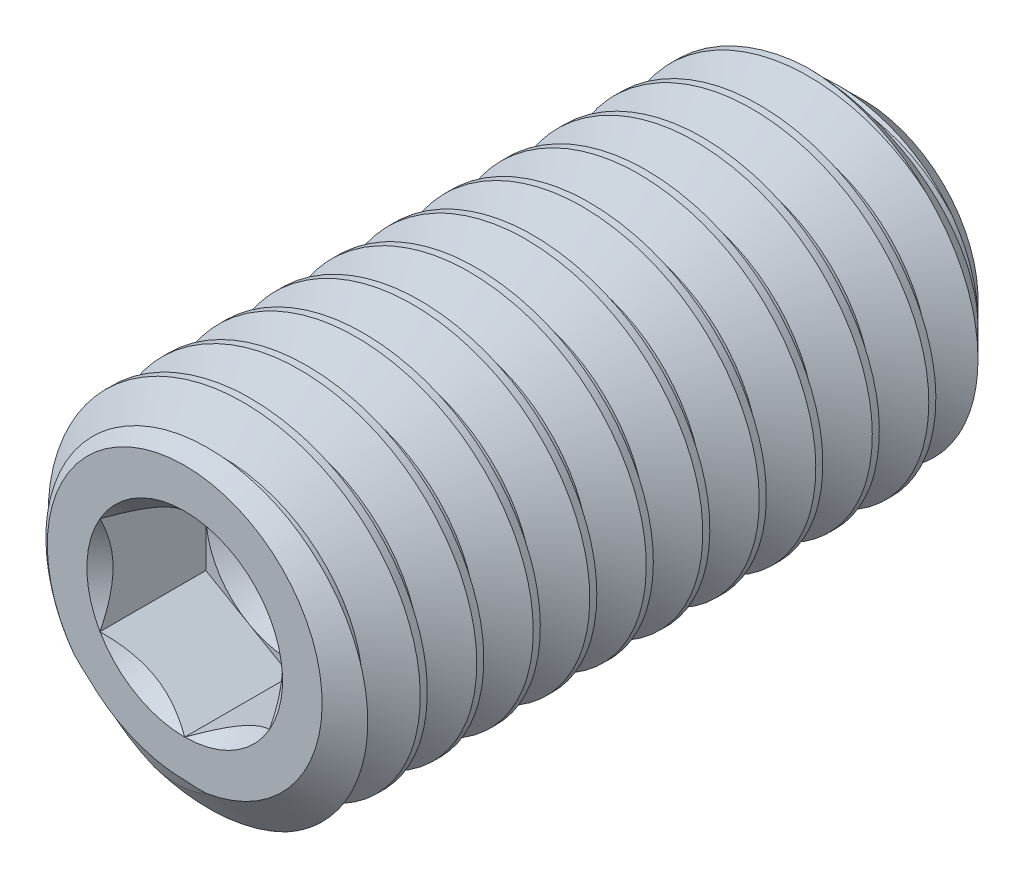
SolidWorks part; units mm, degrees
ref_plane "Front" through (0, 0, 0) normal (0, 0, 1) x (1, 0, 0)
ref_plane "Top" through (0, 0, 0) normal (0, 1, 0) x (1, 0, 0)
ref_plane "Right" through (0, 0, 0) normal (1, 0, 0) x (0, 0, -1)
sketch "Sketch22" plane through (0, 0, 0) normal (1, 0, 0) x (0, 0, -1)
  line L0 (-4.7625, 0) -> (-4.7625, 1.9304)
  line L1 (-4.7625, 1.9304) -> (-4.4246, 2.413)
  line L2 (-4.4246, 2.413) -> (3.9688, 2.413)
  line L3 (3.9688, 2.413) -> (4.7625, 1.6193)
  line L4 (-0.2279, 2.413) -> (-0.2279, -2.413) construction
  line L5 (4.7625, 0) -> (-4.7625, 0)
  line L7 (4.7625, 0) -> (4.7625, 1.6193)
  line L10 (-4.7625, 1.9304) -> (-4.7625, -1.9304) construction
  point P13 (-0.2279, 0)
  dimension "Length" = 9.525
  dimension "D3" = 35
  dimension "D1" = 3.8608
  dimension "Dia" = 4.826
  dimension "D2" = 0.7937
  dimension "D4" = 45
revolve "Revolve1" add sketch "Sketch22" angle 360 about L5
ref_plane "Plane1" through (0, 0, -4.7625) normal (0, 0, 1) x (1, 0, 0)
sketch "Sketch27" plane through (0, 0, -4.7625) normal (0, 0, 1) x (1, 0, 0)
  circle A0 centre (0, 0) radius 2.413 construction
  circle A1 centre (0, 0) radius 2.413
curve "Helix/Spiral1" pitch 0.7937 height 10.3188 radius 2.413 centre (0, 0, -4.7625) axis (0, 0, 1) start towards (1, 0, 0)
sketch "Sketch28" plane through (0, 0, 0) normal (1, 0, 0) x (0, 0, -1)
  line L0 (4.7625, 2.413) -> (5.457, 2.413)
  line L1 (5.457, 2.413) -> (5.1594, 1.8974)
  line L2 (5.1594, 1.8974) -> (5.0602, 1.8974)
  line L3 (5.0602, 1.8974) -> (4.7625, 2.413)
  line L4 (4.9113, 2.1552) -> (5.3082, 2.1552) construction
  line L6 (-4.4246, 2.413) -> (3.9688, 2.413) construction
  line L7 (4.7625, 2.6543) -> (4.7625, -2.6543) construction
  dimension "D1" = 0.0992
  dimension "D3" = 60
  dimension "D2" = 0.3969
sweep "Cut-Sweep2" cut profiles "Sketch28" path "Helix/Spiral1" align with end faces yes
sketch "Sketch23" plane through (0, 0, 4.7625) normal (0, 0, 1) x (1, 0, 0)
  line L1 (0, 1.3748) -> (-1.1906, 0.6874)
  line L2 (-1.1906, 0.6874) -> (-1.1906, -0.6874)
  line L3 (-1.1906, -0.6874) -> (0, -1.3748)
  line L4 (0, -1.3748) -> (1.1906, -0.6874)
  line L5 (1.1906, -0.6874) -> (1.1906, 0.6874)
  line L6 (1.1906, 0.6874) -> (0, 1.3748)
  circle A0 centre (0, 0) radius 1.1906 construction
  dimension "Hex" = 2.3813
extrude "Cut-Extrude10" cut sketch "Sketch23" against normal blind 1.4883
sketch "Sketch24" plane through (0, 0, 4.7625) normal (0, 0, 1) x (1, 0, 0)
  circle A0 centre (0, 0) radius 1.3748
extrude "Cut-Extrude11" cut sketch "Sketch24" against normal through all draft 45
sketch "Sketch26" plane through (0, 0, 3.2742) normal (0, 0, 1) x (1, 0, 0)
  circle A0 centre (0, 0) radius 1.1906 construction
  circle A1 centre (0, 0) radius 1.1906
extrude "Cut-Extrude12" cut sketch "Sketch26" against normal through all draft 60
sketch "Sketch30" plane through (0, 0, 0) normal (1, 0, 0) x (0, 0, -1)
  line L0 (-4.4246, 2.413) -> (3.9688, 2.413) construction
  line L1 (-4.7625, 0) -> (-4.7625, 1.9304) construction
  line L2 (4.7625, 0) -> (4.7625, 1.6193) construction
  point P0 (-4.7625, 2.413)
  point P1 (4.7625, 2.413)
  point P2 (4.7625, -2.413)
  point P11 (2.7781, -2.413)
  dimension "D1" = 1.9844
equation "\"D1@Sketch28\" = \"D4@Helix/Spiral1\" * .125"
equation "\"D3@Helix/Spiral1\" = \"Length@Sketch22\" + \"D4@Helix/Spiral1\""
equation "\"D1@Sketch30\" = \"D4@Helix/Spiral1\" * 2.5"
equation "\"hex Depth@Cut-Extrude10\" = \"Hex@Sketch23\" * .625"
equation "\"D2@Sketch28\" = \"D4@Helix/Spiral1\" * .5"
equation "\"D1@Sketch22\" = \"Dia@Sketch22\" * .8"
equation "\"D2@Sketch22\" = \"D4@Helix/Spiral1\""
